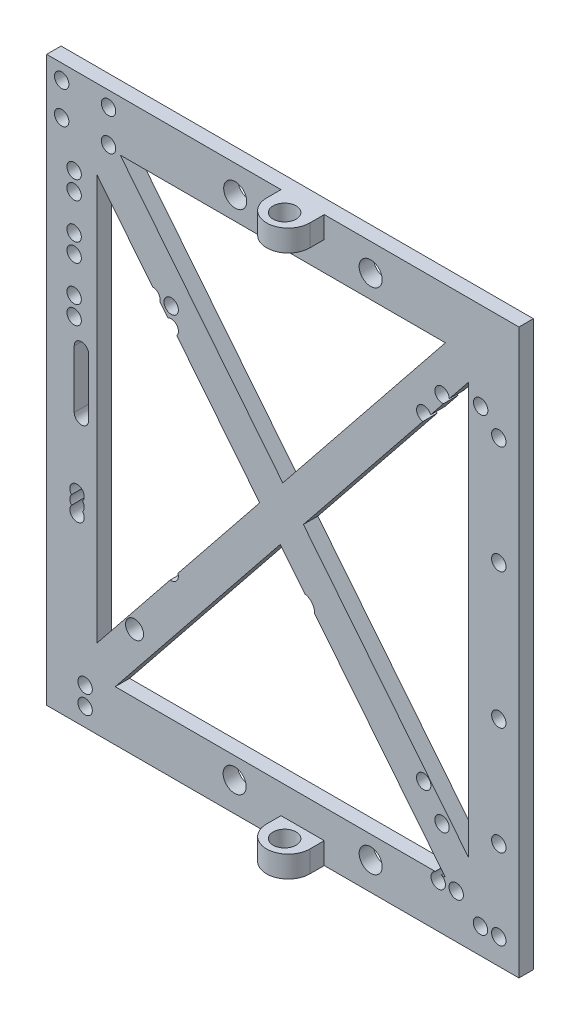
SolidWorks part; units mm, degrees
ref_plane "Front Plane" through (0, 0, 0) normal (0, 0, 1) x (1, 0, 0)
ref_plane "Top Plane" through (0, 0, 0) normal (0, 1, 0) x (1, 0, 0)
ref_plane "Right Plane" through (0, 0, 0) normal (1, 0, 0) x (0, 0, -1)
sketch "Sketch3" plane through (0, 0, 0) normal (0, 0, 1) x (1, 0, 0)
  line L0 (-58.532, 67.237) -> (-58.532, 10.995)
  line L1 (-65.532, 78.232) -> (0, 78.232)
  line L2 (-65.532, 78.232) -> (-65.532, 0)
  line L3 (-65.532, 0) -> (0, 0)
  line L4 (0, 78.232) -> (0, 0)
  line L5 (-56.0191, 7) -> (-10.2051, 7)
  line L6 (-7, 68.0998) -> (-7, 10.995)
  line L8 (-59.706, 45.116) -> (-59.706, 37.116)
  line L9 (-58.532, 71.232) -> (-7, 7) construction
  line L10 (-7, 71.232) -> (-58.532, 7) construction
  line L11 (-55.3269, 71.232) -> (-32.766, 43.111)
  line L12 (-58.532, 67.237) -> (-35.9711, 39.116)
  line L13 (-56.0191, 7) -> (-33.1121, 35.5524)
  line L14 (-58.532, 10.995) -> (-35.9711, 39.116)
  line L15 (-58.532, 71.232) -> (-58.532, 7) construction
  line L16 (-58.532, 7) -> (-7, 7) construction
  line L17 (-33.1121, 35.5524) -> (-10.2051, 7)
  line L18 (-32.766, 43.111) -> (-10.2051, 71.232)
  line L19 (-29.907, 39.5474) -> (-7, 10.995)
  line L20 (-29.907, 39.5474) -> (-7, 68.0998)
  line L21 (-58.532, 71.232) -> (-7, 71.232) construction
  line L22 (-55.3269, 71.232) -> (-10.2051, 71.232)
  line L23 (-7, 71.232) -> (-7, 7) construction
  line L25 (-61.706, 37.116) -> (-61.706, 45.116)
  circle A0 centre (-61.722, 66.169) radius 1
  circle A1 centre (-61.722, 63.629) radius 1
  circle A2 centre (-61.722, 58.669) radius 1
  circle A3 centre (-61.722, 56.129) radius 1
  circle A4 centre (-61.722, 51.169) radius 1
  circle A6 centre (-63.448, 76.164) radius 1
  circle A7 centre (-63.448, 71.664) radius 1
  circle A8 centre (-56.948, 71.664) radius 1
  circle A9 centre (-56.948, 76.164) radius 1
  circle A10 centre (-39.37, 74.422) radius 1.6
  circle A11 centre (-20.574, 74.422) radius 1.6
  circle A12 centre (-5.3091, 66.04) radius 1
  circle A13 centre (-2.794, 63.504) radius 1
  circle A14 centre (-2.794, 48.514) radius 1
  circle A15 centre (-2.794, 29.718) radius 1
  circle A16 centre (-2.794, 14.728) radius 1
  circle A17 centre (-2.799, 3.556) radius 1
  circle A18 centre (-5.339, 3.556) radius 1
  circle A19 centre (-8.7009, 6.096) radius 1
  circle A20 centre (-11.2009, 6.096) radius 1
  circle A21 centre (-20.574, 3.8909) radius 1.6
  circle A22 centre (-39.4509, 4.064) radius 1.6
  circle A23 centre (-60.198, 5.075) radius 1
  circle A24 centre (-60.198, 2.535) radius 1
  circle A25 centre (-61.32, 25.146) radius 1
  circle A26 centre (-61.32, 26.416) radius 1
  circle A27 centre (-61.32, 27.686) radius 1
  arc A28 (-61.706, 37.116) -> (-59.706, 37.116) centre (-60.706, 37.116) ccw
  arc A32 (-59.706, 45.116) -> (-61.706, 45.116) centre (-60.706, 45.116) ccw
  circle A33 centre (-61.722, 48.629) radius 1
  circle A34 centre (-48.255, 56.627) radius 1
  circle A35 centre (-13.213, 17.018) radius 1
  circle A36 centre (-10.668, 13.208) radius 1
  circle A37 centre (-48.26, 24.628) radius 1
  arc A39 (-47.4775, 53.4581) -> (-48.7004, 54.9823) centre (-48.255, 54.087) ccw
  arc A40 (-49.825, 56.3841) -> (-50.8218, 57.6266) centre (-50.795, 56.627) ccw
  circle A41 centre (-13.203, 61.214) radius 1
  circle A42 centre (-10.668, 64.77) radius 1
  circle A43 centre (-29.959, 29.718) radius 1.6
  circle A44 centre (-53.34, 15.24) radius 1.25
  dimension "D2" = 2
  dimension "D3" = 3.2
  dimension "D8" = 2.5
  dimension "D9" = 2
  dimension "D1" = 7
  dimension "D4" = 2.5
  dimension "D5" = 2.5
  dimension "D6" = 2.5
extrude "Boss-Extrude10" add sketch "Sketch3" along normal blind 2 contours L4 L1 L2 L3 A44 A43 L17 L5 A20 L13 A42 L20 L6 L19 A41 A40 L12 A39 L14 A37 L0 A36 A35 A34 A33 A32 L8 A28 L25 A27 A26 A25 region at (-32.422, 39.1083, 0)
sketch3d "3DSketch1"
  line L0 (0, 0, 2) -> (0, 0, 0) construction
  line L2 (-20.574, 0, 0) -> (-20.574, 0, 2)
  line L3 (-65.532, 0, 0) -> (0, 0, 0) construction
  line L4 (-65.532, 0, 2) -> (0, 0, 2) construction
  dimension "D1" = 20.574
ref_plane "Plane1" through (0, 39.116, 0) normal (0, 1, 0) x (1, 0, 0)
sketch "Sketch5" plane through (0, 0, 0) normal (0, -1, 0) x (1, 0, 0)
  line L0 (-20.574, 2) -> (-20.574, 0)
  line L1 (-39.454, 2) -> (-39.454, 0)
  line L2 (-65.532, 2) -> (0, 2) construction
  line L3 (36.0426, 0) -> (-36.0426, 0) construction
  line L4 (-39.454, 1) -> (-20.574, 1) construction
  line L11 (-33.014, 2) -> (-27.014, 2)
  line L12 (-30.014, 2) -> (-30.014, 7) construction
  line L13 (-27.014, 2) -> (-27.014, 4)
  line L14 (-33.014, 2) -> (-33.014, 4)
  line L15 (-27.014, 2) -> (-27.014, 4)
  line L16 (-33.014, 2) -> (-33.014, 4)
  arc A2 (-33.014, 4) -> (-27.014, 4) centre (-30.014, 4) cw
  circle A3 centre (-30.014, 4.5) radius 1.6
  point P23 (0, 0)
  line M8 (-65.532, 0) -> (0, 0)
  line M10 (0, 2) -> (-65.532, 2)
  dimension "D1" = 18.88
extrude "Boss-Extrude11" add sketch "Sketch5" against normal blind 3 contours M8 | A2 L14 L13 A3 M10 region at (-30.014, 0, 2.0781)
mirror "Mirror1" about plane through (0, 39.116, 0) normal (0, 1, 0) of "Boss-Extrude11"
